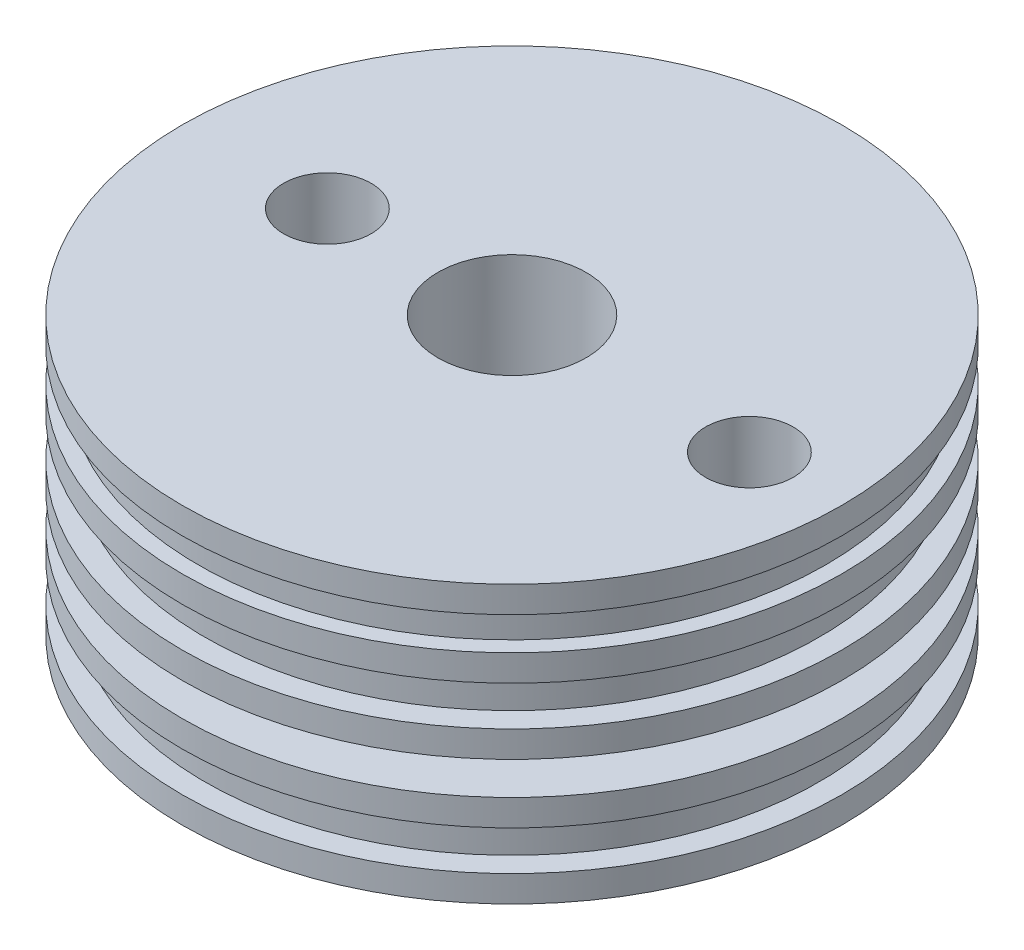
SolidWorks part; units mm, degrees
material "6061-T6 (SS)"
ref_plane "Front Plane" through (0, 0, 0) normal (0, 0, 1) x (1, 0, 0)
ref_plane "Top Plane" through (0, 0, 0) normal (0, 1, 0) x (1, 0, 0)
ref_plane "Right Plane" through (0, 0, 0) normal (1, 0, 0) x (0, 0, -1)
sketch "Sketch1" plane through (0, 0, 0) normal (0, 0, 1) x (1, 0, 0)
  line L0 (0, 26.246) -> (0, -13.9825) construction
  line L2 (-31.75, 12.7) -> (-29.591, 12.7)
  line L3 (-29.591, 12.7) -> (-29.591, 8.89)
  line L4 (-29.591, 8.89) -> (-31.75, 8.89)
  line L5 (-31.75, 8.89) -> (-31.75, 6.35)
  line L6 (-31.75, 6.35) -> (-19.05, 6.35)
  line L7 (-19.05, 6.35) -> (-19.05, 3.175)
  line L8 (-19.05, 3.175) -> (-31.75, 3.175)
  line L9 (-31.75, 3.175) -> (-31.75, 0.635)
  line L10 (-31.75, 0.635) -> (-29.591, 0.635)
  line L11 (-29.591, 0.635) -> (-29.591, -3.175)
  line L12 (-29.591, -3.175) -> (-31.75, -3.175)
  line L13 (-31.75, -3.175) -> (-31.75, -5.715)
  line L14 (-31.75, -5.715) -> (-25.4, -5.715)
  line L16 (-25.4, 0) -> (0, 0)
  line L17 (0, 0) -> (0, 20.955)
  line L19 (-25.4, -5.715) -> (-25.4, 0)
  line L22 (-31.75, 20.955) -> (0, 20.955)
  line L23 (-31.75, 20.955) -> (-31.75, 18.415)
  line L24 (-31.75, 15.24) -> (-31.75, 12.7)
  line L25 (-31.75, 18.415) -> (-30.226, 18.415)
  line L27 (-31.75, 15.24) -> (-30.226, 15.24)
  line L28 (-30.226, 18.415) -> (-30.226, 15.24)
  dimension "D1" = 2.54
  dimension "D2" = 63.5
  dimension "D3" = 3.81
  dimension "D4" = 2.159
  dimension "D5" = 3.175
  dimension "D6" = 50.8
  dimension "D8" = 3.175
  dimension "D9" = 12.7
  dimension "D10" = 3.175
  dimension "D11" = 1.524
revolve "Revolve1" add sketch "Sketch1" angle 360 about L0
hole_wizard "Pipe Tap Drill for 1/8 Tap1" positions "Sketch2" profile "Sketch3" hole size "1/8" standard "ANSI Inch"
sketch "Sketch2" plane through (0, 20.955, 0) normal (0, 1, 0) x (1, 0, 0)
  point P0 (22.86, 0)
  dimension "D1" = 22.86
sketch "Sketch3" plane through (22.86, 20.955, 0) normal (1, 0, 0) x (0, 0, 1)
  line L0 (0, 0) -> (0, 17.78)
  line L1 (0, 17.78) -> (4.2164, 15.2465)
  line L2 (4.2164, 15.2465) -> (4.2164, 0)
  line L5 (4.2164, 0) -> (0, 0)
  line L10 (0, 17.78) -> (-4.2164, 15.2465) construction
  line L11 (0, -6.35) -> (0, 107.95) construction
  dimension "Hole Dia." = 8.4328
  dimension "Hole Depth" = 17.78
  dimension "Drill Angle" = 118
hole_wizard "Pipe Tap Drill for 3/8 Tap2" positions "Sketch4" profile "Sketch5" hole size "3/8" standard "ANSI Inch"
sketch "Sketch4" plane through (0, 20.955, 0) normal (0, 1, 0) x (1, 0, 0)
  point P0 (0, 0)
sketch "Sketch5" plane through (0, 20.955, 0) normal (1, 0, 0) x (0, 0, 1)
  line L0 (0, 0) -> (0, 16.9886)
  line L1 (0, 16.9886) -> (7.1374, 12.7)
  line L2 (7.1374, 12.7) -> (7.1374, 0)
  line L5 (7.1374, 0) -> (0, 0)
  line L10 (0, 16.9886) -> (-7.1374, 12.7) construction
  line L11 (0, -6.35) -> (0, 107.95) construction
  dimension "Hole Dia." = 14.2748
  dimension "Hole Depth" = 12.7
  dimension "Drill Angle" = 118
hole_wizard "#39 (0.0995) Diameter Hole1" positions "Sketch6" profile "Sketch7" hole size "#39" standard "ANSI Inch"
sketch "Sketch6" plane through (0, 0, 0) normal (0, -1, 0) x (-1, 0, 0)
  line L0 (-5.4993, -3.175) -> (0, 0)
  line L3 (0, 0) -> (0, -4.8776)
  point P0 (-5.4993, -3.175)
  dimension "D1" = 6.35
  dimension "D2" = 60
sketch "Sketch7" plane through (5.4993, 0, 3.175) normal (1, 0, 0) x (0, 0, -1)
  line L0 (0, 0) -> (0, 11.176)
  line L1 (0, 11.176) -> (1.2636, 10.4167)
  line L2 (1.2636, 10.4167) -> (1.2636, 0)
  line L5 (1.2636, 0) -> (0, 0)
  line L10 (0, 11.176) -> (-1.2637, 10.4167) construction
  line L11 (0, -6.35) -> (0, 107.95) construction
  dimension "Hole Dia." = 2.5273
  dimension "Hole Depth" = 11.176
  dimension "Drill Angle" = 118
pattern_circular "CirPattern4" count 3 over 360 about axis through (0, 26.246, 0) along (0, 1, 0) of "#39 (0.0995) Diameter Hole1"
hole_wizard "Pipe Tap Drill for 1/8 Tap2" positions "Sketch8" profile "Sketch9" hole size "1/8" standard "ANSI Inch"
sketch "Sketch8" plane through (0, 20.955, 0) normal (0, 1, 0) x (1, 0, 0)
  point P0 (-17.78, 0)
  dimension "D1" = 17.78
sketch "Sketch9" plane through (-17.78, 20.955, 0) normal (1, 0, 0) x (0, 0, 1)
  line L0 (0, 0) -> (0, 12.7)
  line L1 (0, 12.7) -> (4.2164, 10.1665)
  line L2 (4.2164, 10.1665) -> (4.2164, 0)
  line L5 (4.2164, 0) -> (0, 0)
  line L10 (0, 12.7) -> (-4.2164, 10.1665) construction
  line L11 (0, -6.35) -> (0, 107.95) construction
  dimension "Hole Dia." = 8.4328
  dimension "Hole Depth" = 12.7
  dimension "Drill Angle" = 118
ref_axis "Axis2" through (0, 18.3452, 0) along (0, -1, 0)
ref_plane "Plane3" through (0, 0, 0) normal (0.9239, 0, 0.3827) x (0, -1, 0)
ref_axis "Axis1" through (0, 0, 34.925) along (0, 0, -1)
ref_axis "Axis3" through (11.5731, 0, -27.94) along (-0.3827, 0, 0.9239)
ref_plane "Plane1" through (0, 0, 0) normal (-0.6533, -0.7071, -0.2706) x (-0.3827, 0, 0.9239)
hole_wizard "1/16 (0.0625) Diameter Hole1" positions "Sketch39" profile "Sketch40" hole size "1/16" standard "ANSI Inch" end condition up to next
sketch "Sketch39" plane through (0, -5.715, 0) normal (0, -1, 0) x (-1, 0, 0)
  line L0 (0, 0) -> (-17.5976, -10.16)
  line L2 (0, 0) -> (-36.4531, 0)
  line L4 (-17.5976, -10.16) -> (-27.4963, -15.875)
  circle A0 centre (0, 0) radius 31.75 construction
  point P0 (-17.5976, -10.16)
  dimension "D1" = 30
  dimension "D2" = 20.32
sketch "Sketch40" plane through (17.5976, -5.715, 10.16) normal (1, 0, 0) x (0, 0, -1)
  line L0 (0, 0) -> (0, 8.89)
  line L1 (0, 8.89) -> (0.7937, 8.89)
  line L2 (0.7937, 8.89) -> (0.7937, 0)
  line L5 (0.7937, 0) -> (0, 0)
  line L11 (0, -6.35) -> (0, 107.95) construction
  dimension "Thru Hole Dia." = 1.5875
  dimension "Thru Hole Depth" = 8.89
ref_plane "Plane2" through (0, 0, 0) normal (0.5, -0.866, 0) x (0, 0, -1)
hole_wizard "1/4-20 Tapped Hole1" positions "Sketch32" profile "Sketch33" tap size "1/4-20" standard "ANSI Inch"
sketch "Sketch32" plane through (0, 0, 0) normal (0, -1, 0) x (-1, 0, 0)
  point P0 (0, 0)
sketch "Sketch33" plane through (0, 0, 0) normal (1, 0, 0) x (0, 0, -1)
  line L0 (0, 0) -> (0, 12.7)
  line L1 (0, 12.7) -> (2.5527, 11.1662)
  line L2 (2.5527, 11.1662) -> (2.5527, 0)
  line L5 (2.5527, 0) -> (0, 0)
  line L10 (0, 12.7) -> (-2.5527, 11.1662) construction
  line L11 (0, -6.35) -> (0, 107.95) construction
  dimension "Tap Drill Dia." = 5.1054
  dimension "Tap Drill Depth" = 12.7
  dimension "Drill Angle" = 118
cosmetic thread "Hole Thread1" parameters "D1"=12.7, "D2"=6.35
hole_wizard "#29 (0.136) Diameter Hole4" positions "Sketch36" profile "Sketch37" hole size "#29" standard "ANSI Inch"
sketch "Sketch36" plane through (0, -5.715, 0) normal (0, -1, 0) x (-1, 0, 0)
  point P0 (15.24, 0)
  dimension "D1" = 15.24
sketch "Sketch37" plane through (-15.24, -5.715, 0) normal (1, 0, 0) x (0, 0, -1)
  line L0 (0, 0) -> (0, 18.8178)
  line L1 (0, 18.8178) -> (1.7272, 17.78)
  line L2 (1.7272, 17.78) -> (1.7272, 0)
  line L5 (1.7272, 0) -> (0, 0)
  line L10 (0, 18.8178) -> (-1.7272, 17.78) construction
  line L11 (0, -6.35) -> (0, 107.95) construction
  dimension "Hole Dia." = 3.4544
  dimension "Hole Depth" = 17.78
  dimension "Drill Angle" = 118
sketch "Sketch38" plane through (0, -5.715, 0) normal (0, -1, 0) x (1, 0, 0)
  circle A0 centre (-15.24, 0) radius 2.3876
  dimension "D1" = 4.7752
  dimension "D2" = 15.24
extrude "Cut-Extrude3" [suppressed] cut sketch "Sketch38" against normal blind 7.62
sketch "Sketch41" plane through (0, -5.715, 0) normal (0, -1, 0) x (1, 0, 0)
  line L0 (0, 0) -> (17.6649, 4.7333) construction
  line L1 (17.6649, 4.7333) -> (30.6681, 8.2175) construction
  line L2 (0, 0) -> (36.9054, 0) construction
  circle A1 centre (17.6649, 4.7333) radius 1.5875
  circle A2 centre (0, 0) radius 31.75 construction
  dimension "D3" = 3.175
  dimension "D1" = 13.462
  dimension "D2" = 15
extrude "Cut-Extrude4" [suppressed] cut sketch "Sketch41" against normal blind 4.4768
pattern_circular "CirPattern3" count 3 over 360 about axis through (0, 26.246, 0) along (0, 1, 0) of "1/16 (0.0625) Diameter Hole1"
